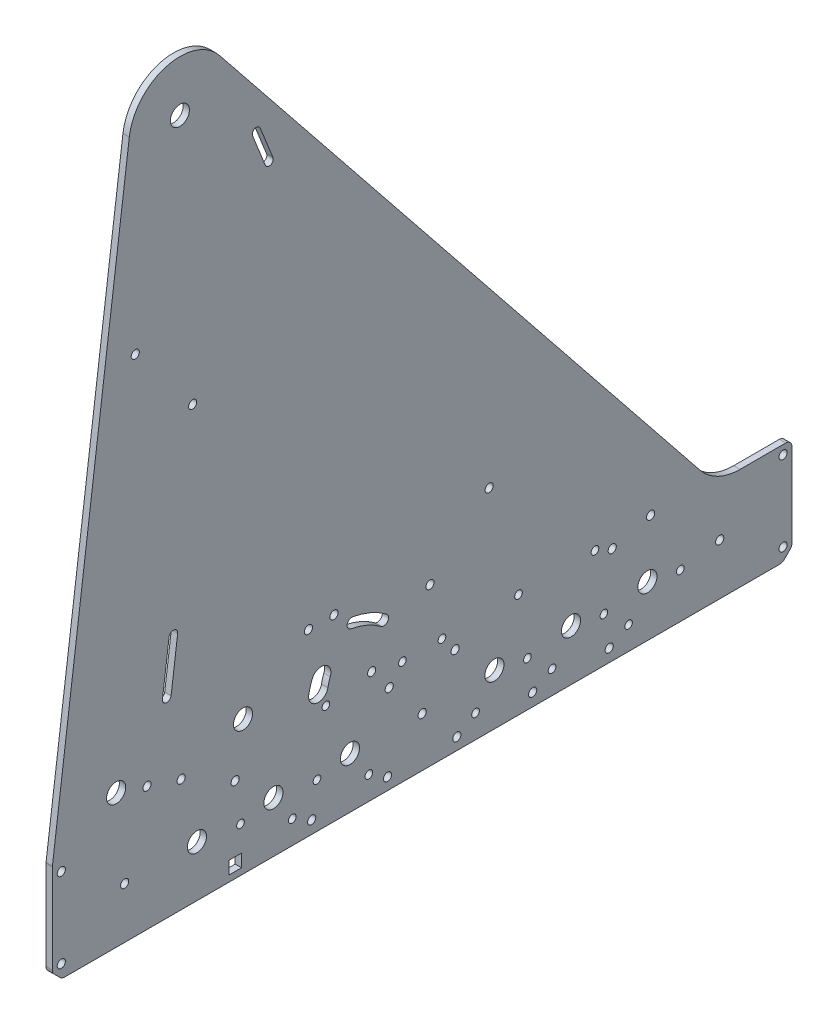
SolidWorks part; units mm, degrees
ref_plane "Front Plane" through (0, 0, 0) normal (0, 0, 1) x (1, 0, 0)
ref_plane "Top Plane" through (0, 0, 0) normal (0, 1, 0) x (1, 0, 0)
ref_plane "Right Plane" through (0, 0, 0) normal (1, 0, 0) x (0, 0, -1)
sketch "Sketch1" plane through (0, 0, 0) normal (1, 0, 0) x (0, 0, -1)
  line L0 (-184.15, -24.6062) -> (184.15, -24.6062)
  line L1 (184.15, -24.6062) -> (184.15, 26.1938)
  line L2 (184.15, 26.1938) -> (146.05, 26.1937)
  line L5 (-145.839, 321.5609) -> (-184.15, 26.1938)
  line L6 (-184.15, 26.1938) -> (-184.15, -24.6062)
  line L7 (-184.15, 350.0437) -> (184.15, 350.0437) construction
  line L9 (146.05, 26.1937) -> (-100.8314, 334.1803)
  arc A0 (-100.8314, 334.1803) -> (-145.839, 321.5609) centre (-120.65, 318.2937) ccw
  point P8 (0, -24.6062)
  dimension "D1" = 368.3
  dimension "D7" = 25.4
  dimension "D2" = 50.8
  dimension "D3" = 38.1
  dimension "D4" = 24.6062
  dimension "D5" = 374.65
  dimension "D6" = 304.8
  dimension "D8" = 342.9
extrude "Boss-Extrude1" add sketch "Sketch1" along normal blind 3.175
chamfer "Chamfer1" distance 4.7625 angle 45 2 edges at (1.5875, -24.6062, 184.15) (1.5875, -24.6062, -184.15)
fillet "Fillet1" radius 25.4 1 edges at (1.5875, 26.1937, -146.05)
fillet "Fillet2" radius 3.175 2 edges at (1.5875, 26.1938, 184.15) (1.5875, 26.1938, -184.15)
fillet "Fillet3" radius 3.175 4 edges at (1.5875, -19.8438, -184.15) (1.5875, -24.6062, -179.3875) (1.5875, -19.8437, 184.15) (1.5875, -24.6062, 179.3875)
sketch "Sketch30" plane through (3.175, 0, 0) normal (1, 0, 0) x (0, 0, -1)
  circle A8 centre (-89.211, 42.2593) radius 4.7625
  circle A9 centre (-25.1593, 30.6938) radius 2.032
  arc A10 (-51.7173, 35.4892) -> (-50.2741, 40.5715) centre (-25.1593, 30.6938) cw construction
  arc A11 (-54.7652, 42.3379) -> (-56.4665, 36.3468) centre (-25.1593, 30.6938) ccw
  arc A12 (-45.783, 38.8051) -> (-46.9681, 34.6317) centre (-25.1593, 30.6938) ccw
  arc A13 (-45.783, 38.8051) -> (-54.7652, 42.3379) centre (-50.2741, 40.5715) ccw
  arc A14 (-56.4665, 36.3468) -> (-46.9681, 34.6317) centre (-51.7173, 35.4892) ccw
  arc A15 (-34.9881, 56.6661) -> (-19.1131, 49.8125) centre (-41.7582, 19.1724) cw construction
  arc A16 (-17.6789, 51.753) -> (-34.5594, 59.0407) centre (-41.7582, 19.1724) ccw
  arc A17 (-20.5473, 47.8719) -> (-35.4169, 54.2915) centre (-41.7582, 19.1724) ccw
  arc A18 (-20.5473, 47.8719) -> (-17.6789, 51.753) centre (-19.1131, 49.8125) ccw
  arc A19 (-34.5594, 59.0407) -> (-35.4169, 54.2915) centre (-34.9881, 56.6661) ccw
  arc A20 (-19.1131, 49.8125) -> (-34.9881, 56.6661) centre (-41.7582, 19.1724) ccw construction
  circle A21 centre (94.6345, 23.8125) radius 2.032
  circle A22 centre (-56.6241, 64.5541) radius 2.032
  circle A23 centre (-43.9241, 64.5541) radius 2.032
  circle A24 centre (-56.6241, 64.5541) radius 1.905 construction
  circle A25 centre (-43.9241, 64.5541) radius 1.905 construction
  point P7 (-51.1204, 38.0658)
  point P19 (-26.6567, 54.1518)
  dimension "D2" = 9.652
  dimension "D4" = 4.064
  dimension "D1" = 4.064
  dimension ".375" = 9.525
  dimension "D3" = 4.826
extrude "Cut-Extrude9" cut sketch "Sketch30" against normal through all
sketch "Sketch16" plane through (3.175, 0, 0) normal (1, 0, 0) x (0, 0, -1)
  circle A0 centre (112.1746, 0.7937) radius 4.7625
  circle A1 centre (74.0746, 0.7937) radius 4.7625
  circle A2 centre (35.9746, 0.7937) radius 4.7625
  circle A3 centre (-35.9746, 0.7938) radius 4.7625
  circle A4 centre (-74.0746, 0.7938) radius 4.7625
  circle A5 centre (-112.1746, 0.7937) radius 4.7625
  dimension "D1" = 9.525
  dimension "D2" = 9.525
extrude "Cut-Extrude1" cut sketch "Sketch16" against normal up to next
sketch "Sketch25" plane through (3.175, 0, 0) normal (1, 0, 0) x (0, 0, -1)
  circle A0 centre (102.7672, -13.0003) radius 1.905 construction
  circle A1 centre (86.0486, 27.3622) radius 1.905 construction
  circle A2 centre (128.5804, -2.3081) radius 1.905 construction
  circle A3 centre (102.7672, -13.0003) radius 1.905
  circle A4 centre (86.0486, 27.3622) radius 1.905
  circle A5 centre (128.5804, -2.3081) radius 1.905
  circle A6 centre (64.6672, -13.0003) radius 1.905 construction
  circle A8 centre (-9.8486, 27.3622) radius 1.905 construction
  circle A10 centre (-47.9486, 27.3622) radius 1.905 construction
  circle A11 centre (-90.4804, -2.3081) radius 1.905 construction
  circle A12 centre (-64.6672, -13.0003) radius 1.905 construction
  circle A14 centre (-52.3804, -2.3081) radius 1.905 construction
  circle A15 centre (-26.5672, -13.0003) radius 1.905 construction
  circle A16 centre (9.8486, 27.3622) radius 1.905 construction
  circle A17 centre (26.5672, -13.0003) radius 1.905 construction
  circle A18 centre (47.9486, 27.3622) radius 1.905 construction
  circle A19 centre (52.3804, -2.3081) radius 1.905 construction
  circle A20 centre (90.4804, -2.3081) radius 1.905 construction
  circle A21 centre (-9.8486, 27.3622) radius 1.905
  circle A23 centre (-47.9486, 27.3622) radius 1.905
  circle A24 centre (-90.4804, -2.3081) radius 1.905
  circle A25 centre (-64.6672, -13.0003) radius 1.905
  circle A27 centre (-52.3804, -2.3081) radius 1.905
  circle A28 centre (-26.5672, -13.0003) radius 1.905
  circle A29 centre (9.8486, 27.3622) radius 1.905
  circle A30 centre (26.5672, -13.0003) radius 1.905
  circle A31 centre (47.9486, 27.3622) radius 1.905
  circle A32 centre (64.6672, -13.0003) radius 1.905
  circle A33 centre (52.3804, -2.3081) radius 1.905
  circle A34 centre (90.4804, -2.3081) radius 1.905
extrude "Cut-Extrude4" cut sketch "Sketch25" against normal up to next
sketch "Sketch23" plane through (3.175, 0, 0) normal (1, 0, 0) x (0, 0, -1)
  circle A0 centre (179.705, 21.7488) radius 1.905 construction
  point P0 (-55.0246, -18.3223)
  point P6 (-93.1246, 17.5943)
  point P9 (-17.2515, -18.6426)
  point P12 (-16.4124, 19.3854)
  point P15 (16.4124, 19.3854)
  point P18 (17.2515, -18.6426)
  point P21 (55.0246, -18.3223)
  point P35 (3.8736, 53.6853)
  point P38 (113.7728, 28.6594)
  point P41 (-137.0088, 37.226)
  point P44 (-179.705, 21.7487)
  point P47 (-179.705, -18.0026)
  point P50 (179.705, 21.7488)
  point P53 (179.705, -18.0026)
  point P59 (93.1246, -18.3223)
hole_wizard "#8 (0.16) Diameter Hole1" positions "Sketch23" profile "Sketch24" hole size "#8" standard "ANSI Inch" end condition up to next
sketch "Sketch24" plane through (3.175, -18.3223, 55.0246) normal (0, 1, 0) x (0, 0, -1)
  line L0 (0, 0) -> (0, 3.175)
  line L1 (0, 3.175) -> (2.032, 3.175)
  line L2 (2.032, 3.175) -> (2.032, 0)
  line L5 (2.032, 0) -> (0, 0)
  line L11 (0, -6.35) -> (0, 107.95) construction
  dimension "Thru Hole Dia." = 4.064
  dimension "Thru Hole Depth" = 3.175
sketch "Sketch22" plane through (3.175, 0, 0) normal (1, 0, 0) x (0, 0, -1)
  line L0 (-96.2996, -15.1473) -> (-89.9496, -15.1473) construction
  line L1 (-96.2996, -15.1473) -> (-89.9496, -15.1473)
  line L2 (-96.2996, -15.1473) -> (-96.2996, -21.4973)
  line L3 (-96.2996, -21.4973) -> (-89.9496, -21.4973)
  line L4 (-89.9496, -15.1473) -> (-89.9496, -21.4973)
  line L5 (-96.2996, -15.1473) -> (-89.9496, -21.4973) construction
  line L6 (-96.2996, -21.4973) -> (-89.9496, -15.1473) construction
  line L7 (-89.9496, -15.1473) -> (-89.9496, -19.8734) construction
  point P0 (-93.1246, -18.3223)
  dimension "D1" = 6.35
extrude "Cut-Extrude3" cut sketch "Sketch22" against normal up to next
sketch "Sketch21" plane through (3.175, 0, 0) normal (1, 0, 0) x (0, 0, -1)
  circle A0 centre (-148.1579, 0.7937) radius 2.032
  circle A2 centre (0, 0) radius 2.032
  circle A3 centre (148.1579, 0.7938) radius 2.032
  dimension "D1" = 4.064
extrude "Cut-Extrude2" cut sketch "Sketch21" against normal up to next
sketch "Sketch26" [suppressed] plane through (3.175, 0, 0) normal (1, 0, 0) x (0, 0, -1)
  line L0 (-145.839, 321.5609) -> (-184.1236, 26.3971) construction
  line L1 (-178.0724, -24.6062) -> (178.0724, -24.6062) construction
  circle A0 centre (-121.0218, 216.6937) radius 15.24
  dimension "D1" = 30.48
  dimension "D2" = 38.1
  dimension "D3" = 241.3
extrude "Cut-Extrude5" [suppressed] cut sketch "Sketch26" against normal through all
sketch "Sketch27" plane through (3.175, 0, 0) normal (1, 0, 0) x (0, 0, -1)
  circle A0 centre (-120.65, 318.2937) radius 4.7625
  dimension "D1" = 9.525
extrude "Cut-Extrude6" cut sketch "Sketch27" against normal through all
sketch "Sketch28" plane through (3.175, 0, 0) normal (1, 0, 0) x (0, 0, -1)
  line L0 (-120.65, 318.2937) -> (-103.5612, 277.2599) construction
  line L1 (-103.5612, 277.2599) -> (-86.3654, 258.566) construction
  line L2 (-86.3654, 258.566) -> (-90.1612, 246.4465) construction
  line L3 (-90.1612, 246.4465) -> (-93.9569, 234.327) construction
  line L4 (-145.839, 321.5609) -> (-184.1236, 26.3971) construction
  circle A0 centre (-93.9569, 234.327) radius 2.032
  circle A1 centre (-90.1612, 246.4465) radius 2.032
  circle A2 centre (-86.3654, 258.566) radius 2.0955
  circle A3 centre (-103.5612, 277.2599) radius 2.032
  dimension "D4" = 4.064
  dimension "D5" = 4.191
  dimension "D6" = 4.064
  dimension "D1" = 25.4
  dimension "D2" = 44.45
  dimension "D3" = 12.7
  dimension "D7" = 30
  dimension "D8" = 120
  dimension "D9" = 160
extrude "Cut-Extrude7" [suppressed] cut sketch "Sketch28" against normal through all
sketch "Sketch29" plane through (3.175, 0, 0) normal (1, 0, 0) x (0, 0, -1)
  line L1 (-82.55, 292.1) -> (-76.2, 276.225) construction
  line L2 (-80.6633, 292.8547) -> (-74.3133, 276.9797)
  line L3 (-84.4367, 291.3453) -> (-78.0867, 275.4703)
  arc A4 (-80.6633, 292.8547) -> (-84.4367, 291.3453) centre (-82.55, 292.1) ccw
  arc A5 (-78.0867, 275.4703) -> (-74.3133, 276.9797) centre (-76.2, 276.225) ccw
  point P8 (-79.375, 284.1625)
  dimension "D1" = 276.225
  dimension "D2" = 2.032
  dimension "D3" = 76.2
  dimension "D4" = 82.55
  dimension "D5" = 292.1
sketch "Sketch31" plane through (0, 0, 0) normal (-1, 0, 0) x (0, 0, 1)
  circle A1 centre (114.3, 190.5) radius 2.032
  dimension "D1" = 114.3
  dimension "D6" = 4.064
  dimension "D2" = 190.5
extrude "Cut-Extrude10" cut sketch "Sketch31" against normal through all
sketch "Sketch34" plane through (0, 0, 0) normal (-1, 0, 0) x (0, 0, 1)
  line L3 (123.9045, 95.7355) -> (127.1716, 70.5465) construction
  line L4 (126.0455, 96.0132) -> (129.3127, 70.8242)
  line L5 (121.7634, 95.4578) -> (125.0306, 70.2688)
  line L6 (145.839, 321.5609) -> (184.1236, 26.3971) construction
  arc A2 (126.0455, 96.0132) -> (121.7634, 95.4578) centre (123.9045, 95.7355) ccw
  arc A3 (125.0306, 70.2688) -> (129.3127, 70.8242) centre (127.1716, 70.5465) ccw
  point P9 (125.538, 83.141)
  point P18 (114.3, 190.5)
  dimension "D8" = 4.318
  dimension "D6" = 50.8
  dimension "D7" = 25.4
  dimension "D9" = 95.25
extrude "Cut-Extrude12" cut sketch "Sketch34" against normal through all
sketch "Sketch38" plane through (3.175, 0, 0) normal (1, 0, 0) x (0, 0, -1)
  line L0 (-184.15, 25.9887) -> (-184.15, -18.5286) construction
  line L1 (-178.0724, -24.6062) -> (178.0724, -24.6062) construction
  circle A0 centre (-152.4, 42.0688) radius 4.7625
  dimension "D1" = 31.75
  dimension "D3" = 9.525
  dimension "D2" = 66.675
extrude "Cut-Extrude14" cut sketch "Sketch38" against normal through all
sketch "Sketch37" plane through (3.175, 0, 0) normal (1, 0, 0) x (0, 0, -1)
  circle A0 centre (33.3375, 80.645) radius 2.032
  circle A8 centre (0, 0) radius 2.032 construction
  dimension "D1" = 4.064
  dimension "D2" = 33.3375
  dimension "D3" = 80.645
extrude "Cut-Extrude13" cut sketch "Sketch37" against normal through all
extrude "Cut-Extrude15" cut sketch "Sketch29" against normal through all
sketch "Sketch40" plane through (3.175, 0, 0) normal (1, 0, 0) x (0, 0, -1)
  circle A0 centre (-120.015, 31.75) radius 2.032
  dimension "D1" = 4.064
  dimension "D2" = 120.015
  dimension "D3" = 31.75
extrude "Cut-Extrude16" cut sketch "Sketch40" against normal through all
sketch "Sketch41" [suppressed] plane through (3.175, 0, 0) normal (1, 0, 0) x (0, 0, -1)
  line L0 (-120.65, 318.2937) -> (-98.425, 279.7989) construction
  line L1 (-98.425, 279.7989) -> (-77.6666, 265.1617) construction
  line L2 (-120.65, 318.2937) -> (-60.41, 318.2937) construction
  circle A0 centre (-120.65, 318.2937) radius 25.4 construction
  circle A1 centre (-98.425, 279.7989) radius 19.05 construction
  circle A2 centre (-77.6666, 265.1617) radius 6.35 construction
  circle A3 centre (-98.425, 279.7989) radius 2.032
  circle A4 centre (-77.6666, 265.1617) radius 2.032
  dimension "D1" = 50.8
  dimension "D2" = 38.1
  dimension "D3" = 12.7
  dimension "D4" = 4.064
  dimension "D5" = 60
extrude "Cut-Extrude17" [suppressed] cut sketch "Sketch41" against normal through all
sketch "Sketch43" plane through (3.175, 0, 0) normal (1, 0, 0) x (0, 0, -1)
  line L0 (-152.4, 200.025) -> (-123.6487, 200.025) construction
  line L1 (-115.9779, 252.0412) -> (-152.4, 200.025) construction
  circle A0 centre (-152.4, 200.025) radius 2.032
  arc A1 (-143.2813, 262.8669) -> (-96.4668, 230.087) centre (-152.4, 200.025) cw construction
  arc A2 (-92.2158, 232.3717) -> (-142.5883, 267.6428) centre (-152.4, 200.025) ccw
  arc A3 (-100.7177, 227.8023) -> (-143.9743, 258.0909) centre (-152.4, 200.025) ccw
  arc A4 (-100.7177, 227.8023) -> (-92.2158, 232.3717) centre (-96.4668, 230.087) ccw
  arc A5 (-142.5883, 267.6428) -> (-143.9743, 258.0909) centre (-143.2813, 262.8669) ccw
  point P6 (-115.9779, 252.0412)
  dimension "D1" = 4.064
  dimension "D4" = 4.826
  dimension "D2" = 200.025
  dimension "D3" = 152.4
  dimension "D5" = 63.5
  dimension "D6" = 57.15
  dimension "D7" = 55
extrude "Cut-Extrude19" [suppressed] cut sketch "Sketch43" against normal through all
sketch "Sketch44" plane through (3.175, 0, 0) normal (1, 0, 0) x (0, 0, -1)
  circle A0 centre (-142.875, 226.3775) radius 2.032
  dimension "D1" = 4.064
  dimension "D2" = 142.875
  dimension "D3" = 226.3775
extrude "Cut-Extrude20" cut sketch "Sketch44" against normal through all
sketch "Sketch50" [suppressed] plane through (0, 0, 0) normal (-1, 0, 0) x (0, 0, 1)
  line L0 (98.7055, 213.2489) -> (51.4524, 213.2489) construction
  line L1 (98.7055, 211.2169) -> (51.4524, 211.2169)
  line L2 (98.7055, 215.2809) -> (51.4524, 215.2809)
  arc A1 (98.7055, 211.2169) -> (98.7055, 215.2809) centre (98.7055, 213.2489) ccw
  arc A2 (51.4524, 215.2809) -> (51.4524, 211.2169) centre (51.4524, 213.2489) ccw
  point P3 (75.079, 213.2489)
  dimension "D1" = 2.032
  dimension "D2" = 98.7055
  dimension "D3" = 213.2489
  dimension "D4" = 47.253
extrude "Cut-Extrude22" [suppressed] cut sketch "Sketch50" against normal through all
sketch "Sketch51" [suppressed] plane through (3.175, 0, 0) normal (1, 0, 0) x (0, 0, -1)
  circle A0 centre (-114.3, 215.9) radius 2.032
  circle A1 centre (-114.3, 165.1) radius 2.032
  dimension "D1" = 114.3
  dimension "D3" = 50.8
  dimension "D4" = 4.064
  dimension "D2" = 215.9
extrude "Cut-Extrude23" [suppressed] cut sketch "Sketch51" against normal through all
sketch "Sketch52" [suppressed] plane through (0, 0, 0) normal (-1, 0, 0) x (0, 0, 1)
  arc A5 (141.2875, 264.4775) -> (109.814, 245.1467) centre (142.9767, 226.44) ccw construction
  arc A6 (141.1974, 266.5075) -> (108.0442, 246.1451) centre (142.9767, 226.44) ccw
  arc A7 (141.3776, 262.4475) -> (111.5838, 244.1484) centre (142.9767, 226.44) ccw
  arc A8 (141.3776, 262.4475) -> (141.1974, 266.5075) centre (141.2875, 264.4775) ccw
  arc A9 (108.0442, 246.1451) -> (111.5838, 244.1484) centre (109.814, 245.1467) ccw
  point P4 (123.0497, 258.8841)
  dimension "D1" = 38.075
  dimension "D2" = 2.032
  dimension "D3" = 264.4775
  dimension "D4" = 141.2875
  dimension "D5" = 245.1467
  dimension "D6" = 109.814
extrude "Cut-Extrude24" [suppressed] cut sketch "Sketch52" against normal through all
